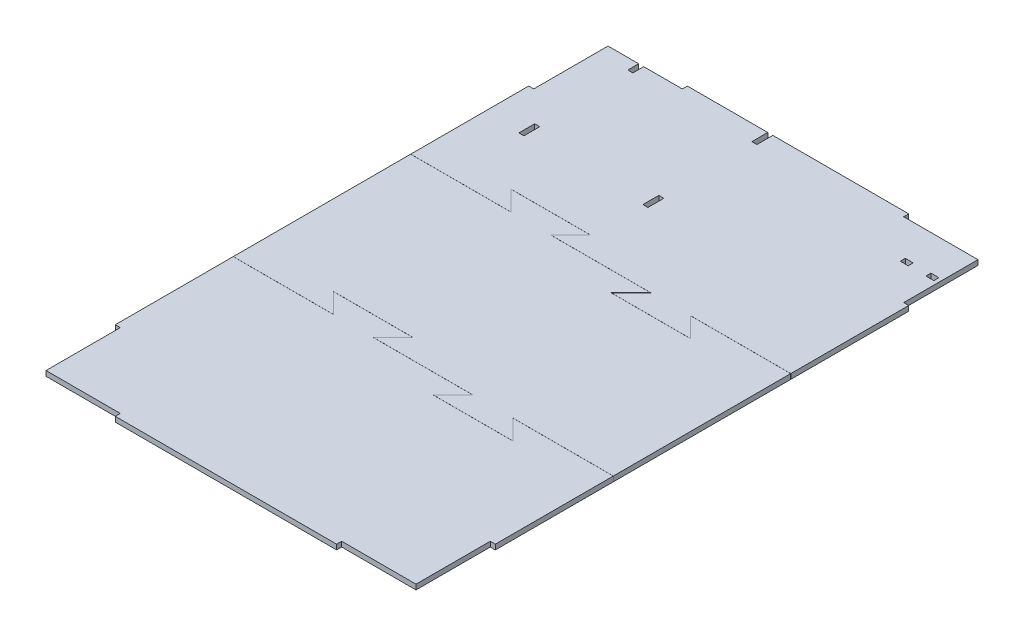
SolidWorks part; units mm, degrees
ref_plane "Front Plane" through (0, 0, 0) normal (0, 0, 1) x (1, 0, 0)
ref_plane "Top Plane" through (0, 0, 0) normal (0, 1, 0) x (1, 0, 0)
ref_plane "Right Plane" through (0, 0, 0) normal (1, 0, 0) x (0, 0, -1)
sketch "Sketch1" plane through (0, 0, 0) normal (0, 1, 0) x (1, 0, 0)
  line L7 (-239.5, -360.5) -> (239.5, -360.5)
  line L8 (-239.5, -360.5) -> (-239.5, 360.5)
  line L9 (-239.5, 360.5) -> (239.5, 360.5)
  line L10 (239.5, -360.5) -> (239.5, 360.5)
  point P0 (0, 0)
  point P3 (239.5, 0)
  point P6 (0, 0)
  point P11 (0, -360.5)
  dimension "D1" = 721
  dimension "D2" = 479
extrude "Boss-Extrude1" add sketch "Sketch1" along normal mid plane 6.35
sketch "Sketch2" plane through (0, 3.175, 0) normal (0, 1, 0) x (1, 0, 0)
  line L0 (-239.5, 360.5) -> (-239.5, 260.5)
  line L1 (-239.5, 360.5) -> (-239.5, -360.5) construction
  line L2 (-239.5, 260.5) -> (-233.15, 260.5)
  line L3 (-233.15, 260.5) -> (-233.15, 354.15)
  line L4 (-233.15, 354.15) -> (-139.5, 354.15)
  line L5 (-139.5, 354.15) -> (-139.5, 360.5)
  line L6 (239.5, 360.5) -> (-239.5, 360.5) construction
  line L7 (-139.5, 360.5) -> (-239.5, 360.5)
  line L8 (239.5, 360.5) -> (139.5, 360.5)
  line L9 (139.5, 360.5) -> (139.5, 354.15)
  line L10 (139.5, 354.15) -> (233.15, 354.15)
  line L11 (233.15, 354.15) -> (233.15, 260.5)
  line L12 (233.15, 260.5) -> (239.5, 260.5)
  line L13 (239.5, -360.5) -> (239.5, 360.5) construction
  line L14 (239.5, 260.5) -> (239.5, 360.5)
  line L15 (239.5, -360.5) -> (239.5, -260.5)
  line L16 (239.5, -260.5) -> (233.15, -260.5)
  line L17 (233.15, -260.5) -> (233.15, -354.15)
  line L18 (233.15, -354.15) -> (139.5, -354.15)
  line L19 (139.5, -354.15) -> (139.5, -360.5)
  line L20 (-239.5, -360.5) -> (239.5, -360.5) construction
  line L21 (139.5, -360.5) -> (239.5, -360.5)
  line L22 (-239.5, -360.5) -> (-139.5, -360.5)
  line L23 (-139.5, -360.5) -> (-139.5, -354.15)
  line L24 (-139.5, -354.15) -> (-233.15, -354.15)
  line L25 (-233.15, -354.15) -> (-233.15, -260.5)
  line L26 (-233.15, -260.5) -> (-239.5, -260.5)
  line L27 (-239.5, -260.5) -> (-239.5, -360.5)
  dimension "D1" = 100
  dimension "D2" = 6.35
extrude "Cut-Extrude1" cut sketch "Sketch2" against normal through all
sketch "Sketch3" plane through (0, -3.175, 0) normal (0, -1, 0) x (1, 0, 0)
  line L0 (233.15, -354.15) -> (233.15, -260.5) construction
  line L1 (139.5, -354.15) -> (233.15, -354.15) construction
  line L2 (139.5, -360.5) -> (-139.5, -360.5) construction
  line L3 (-31.8, -360.5) -> (-38.15, -360.5)
  line L4 (-31.8, -360.5) -> (-31.8, -340.5)
  line L5 (-31.8, -340.5) -> (-38.15, -340.5)
  line L6 (-38.15, -360.5) -> (-38.15, -340.5)
  line L7 (-233.15, -260.5) -> (-233.15, -354.15) construction
  line L8 (185.85, -303.45) -> (195.85, -303.45)
  line L9 (185.85, -303.45) -> (185.85, -309.8)
  line L10 (185.85, -309.8) -> (195.85, -309.8)
  line L11 (195.85, -303.45) -> (195.85, -309.8)
  line L12 (228.15, -303.45) -> (228.15, -309.8)
  line L13 (218.15, -303.45) -> (228.15, -303.45)
  line L14 (218.15, -303.45) -> (218.15, -309.8)
  line L15 (218.15, -309.8) -> (228.15, -309.8)
  line L16 (-188.15, -360.5) -> (-194.5, -360.5)
  line L17 (-188.15, -360.5) -> (-188.15, -340.5)
  line L18 (-188.15, -340.5) -> (-194.5, -340.5)
  line L19 (-194.5, -360.5) -> (-194.5, -340.5)
  line L20 (-31.8, -223.15) -> (-38.15, -223.15)
  line L21 (-31.8, -223.15) -> (-31.8, -203.15)
  line L22 (-31.8, -203.15) -> (-38.15, -203.15)
  line L23 (-38.15, -223.15) -> (-38.15, -203.15)
  line L24 (-188.15, -223.15) -> (-194.5, -223.15)
  line L25 (-188.15, -223.15) -> (-188.15, -203.15)
  line L26 (-188.15, -203.15) -> (-194.5, -203.15)
  line L27 (-194.5, -223.15) -> (-194.5, -203.15)
  dimension "D1" = 10
  dimension "D2" = 6.35
  dimension "D3" = 5
  dimension "D4" = 42.3
  dimension "D5" = 44.35
  dimension "D6" = 6.35
  dimension "D7" = 20
  dimension "D8" = 117.35
  dimension "D9" = 150
  dimension "D10" = 45
extrude "Cut-Extrude2" cut sketch "Sketch3" against normal through all
sketch "Sketch4" plane through (0, 3.175, 0) normal (0, 1, 0) x (1, 0, 0)
  line L0 (-239.5, -111.7667) -> (-113.1667, -111.7667)
  line L1 (-239.5, 111.8667) -> (-113.1667, 111.8667)
  line L2 (-239.5, 260.5) -> (-239.5, -260.5) construction
  line L3 (-113.1667, -111.7667) -> (-138.1667, -86.7667)
  line L4 (-138.1667, -86.7667) -> (-38.1667, -86.7667)
  line L5 (-38.1667, -86.7667) -> (-63.1667, -111.7667)
  line L6 (-63.1667, -111.7667) -> (63.1667, -111.7667)
  line L7 (63.1667, -111.7667) -> (38.1667, -136.7667)
  line L8 (38.1667, -136.7667) -> (138.1667, -136.7667)
  line L9 (138.1667, -136.7667) -> (113.1667, -111.7667)
  line L10 (113.1667, -111.7667) -> (239.5, -111.7667)
  line L11 (-113.1667, 111.8667) -> (-138.1667, 136.8667)
  line L12 (239.5, -260.5) -> (239.5, 260.5) construction
  line L14 (-239.5, -111.8667) -> (-112.9252, -111.8667)
  line L15 (-112.9252, -111.8667) -> (-137.9252, -86.8667)
  line L16 (-137.9252, -86.8667) -> (-38.4081, -86.8667)
  line L17 (-38.4081, -86.8667) -> (-63.4081, -111.8667)
  line L18 (-63.4081, -111.8667) -> (62.9252, -111.8667)
  line L19 (62.9252, -111.8667) -> (37.9252, -136.8667)
  line L20 (37.9252, -136.8667) -> (138.4081, -136.8667)
  line L21 (138.4081, -136.8667) -> (113.4081, -111.8667)
  line L22 (113.4081, -111.8667) -> (239.5, -111.8667)
  line L23 (-239.5, -111.8667) -> (-239.5, -111.7667)
  line L24 (239.5, -111.8667) -> (239.5, -111.7667)
  line L25 (-138.1667, 136.8667) -> (-38.1667, 136.8667)
  line L26 (-38.1667, 136.8667) -> (-63.1667, 111.8667)
  line L27 (-63.1667, 111.8667) -> (63.1667, 111.8667)
  line L28 (63.1667, 111.8667) -> (38.1667, 86.8667)
  line L29 (38.1667, 86.8667) -> (138.1667, 86.8667)
  line L30 (138.1667, 86.8667) -> (113.1667, 111.8667)
  line L31 (113.1667, 111.8667) -> (239.5, 111.8667)
  line L32 (-239.5, 111.7667) -> (-112.9252, 111.7667)
  line L33 (-112.9252, 111.7667) -> (-137.9252, 136.7667)
  line L34 (-137.9252, 136.7667) -> (-38.4081, 136.7667)
  line L35 (-38.4081, 136.7667) -> (-63.4081, 111.7667)
  line L36 (-63.4081, 111.7667) -> (62.9252, 111.7667)
  line L37 (62.9252, 111.7667) -> (37.9252, 86.7667)
  line L38 (37.9252, 86.7667) -> (138.4081, 86.7667)
  line L39 (138.4081, 86.7667) -> (113.4081, 111.7667)
  line L40 (113.4081, 111.7667) -> (239.5, 111.7667)
  line L41 (-239.5, 111.7667) -> (-239.5, 111.8667)
  line L42 (239.5, 111.7667) -> (239.5, 111.8667)
  line L43 (-239.5, -111.7667) -> (-239.5, 111.8667) construction
  line L45 (0, -86.7667) -> (0, -360.5) construction
  line L47 (-139.5, -360.5) -> (139.5, -360.5) construction
  line L48 (0, -136.8667) -> (0, 136.8667) construction
  line L49 (0, 86.7667) -> (0, 360.5) construction
  line L50 (139.5, 360.5) -> (-31.8, 360.5) construction
  dimension "D1" = 100
  dimension "D2" = 25
  dimension "D5" = 2
  dimension "D4" = 0.1
extrude "Cut-Extrude3" cut sketch "Sketch4" against normal through all
delete or keep bodies "Body-Delete/Keep 1" [suppressed] type keep bodies bodies 104
delete or keep bodies "Body-Delete/Keep 2" [suppressed] type keep bodies bodies 105
delete or keep bodies "Body-Delete/Keep 3" [suppressed] type keep bodies bodies 106
